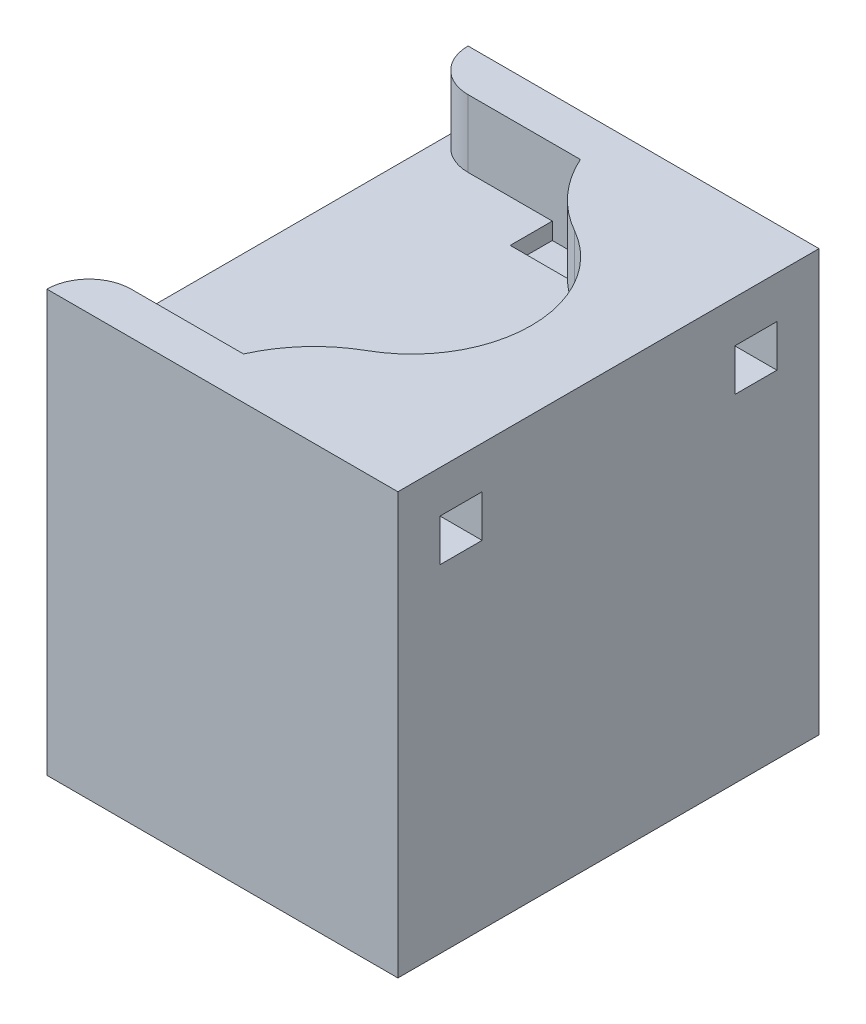
SolidWorks part; units mm, degrees
ref_plane "Front Plane" through (0, 0, 0) normal (0, 0, 1) x (1, 0, 0)
ref_plane "Top Plane" through (0, 0, 0) normal (0, 1, 0) x (1, 0, 0)
ref_plane "Right Plane" through (0, 0, 0) normal (1, 0, 0) x (0, 0, -1)
sketch "Sketch1" plane through (0, 0, 0) normal (0, 1, 0) x (1, 0, 0)
  line L1 (-12.5, -15) -> (12.5, -15)
  line L2 (-12.5, -15) -> (-12.5, 15)
  line L3 (-12.5, 15) -> (12.5, 15)
  line L4 (12.5, -15) -> (12.5, 15)
  line L5 (-12.5, -15) -> (12.5, 15) construction
  line L6 (-12.5, 15) -> (12.5, -15) construction
  point P0 (0, 0)
  dimension "D1" = 25
  dimension "D2" = 30
extrude "Boss-Extrude1" add sketch "Sketch1" along normal blind 30
sketch "Sketch3" plane through (12.5, 0, 0) normal (1, 0, 0) x (0, 0, -1)
  line L0 (15, 30) -> (15, 0) construction
  line L1 (9, 24) -> (12, 24)
  line L2 (9, 24) -> (9, 27)
  line L3 (9, 27) -> (12, 27)
  line L4 (12, 24) -> (12, 27)
  line L5 (-15, 30) -> (15, 30) construction
  line L6 (0, 33.4331) -> (0, -6.7562) construction
  line L7 (-12, 24) -> (-12, 27)
  line L8 (-9, 27) -> (-12, 27)
  line L9 (-9, 24) -> (-9, 27)
  line L10 (-9, 24) -> (-12, 24)
  dimension "D1" = 3
  dimension "D2" = 3
  dimension "D3" = 3
  dimension "D4" = 3
extrude "Cut-Extrude1" cut sketch "Sketch3" against normal blind 16
sketch "Sketch5" plane through (0, 30, 0) normal (0, 1, 0) x (1, 0, 0)
  line L0 (12.5, 15) -> (-12.5, 15) construction
  line L1 (-12.5, -12) -> (-1.5, -12)
  line L2 (-12.5, -12) -> (-12.5, 12)
  line L3 (-12.5, 12) -> (-1.5, 12)
  line L4 (-1.5, -12) -> (-1.5, -8.5)
  line L5 (-12.5, -15) -> (12.5, -15) construction
  line L6 (-12.5, 15) -> (-12.5, -15) construction
  line L7 (-1.5, 8.5) -> (-1.5, 12)
  arc A0 (-1.5, 8.5) -> (-1.5, -8.5) centre (-1.5, 0) cw
  dimension "D5" = 8.5
  dimension "D1" = 3
  dimension "D2" = 11
  dimension "D3" = 3
  dimension "D4" = 0
  dimension "D6" = 12
extrude "Cut-Extrude2" cut sketch "Sketch5" against normal blind 4.8
fillet "Fillet1" radius 10 2 edges at (-1.5, 27.6, 8.5) (-1.5, 27.6, -8.5)
fillet "Fillet2" radius 3 2 edges at (-12.5, 27.6, 12) (-12.5, 27.6, -12)
